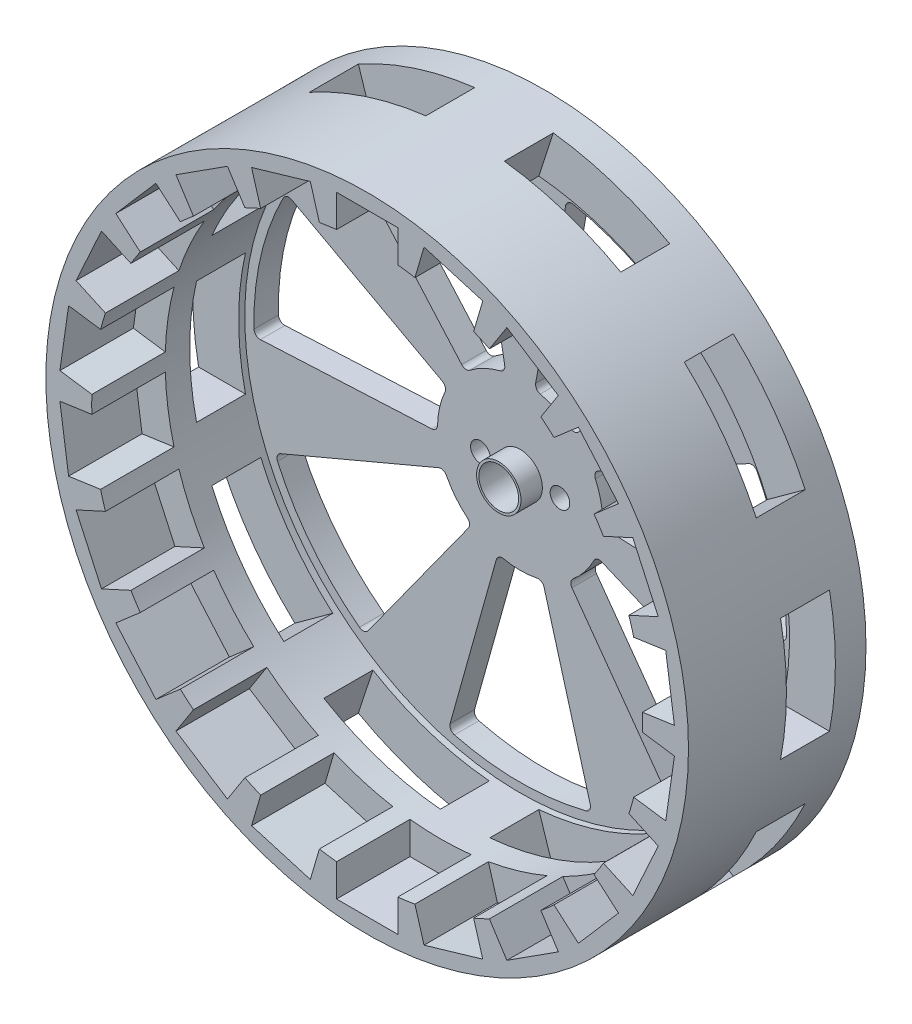
SolidWorks part; units mm, degrees
ref_plane "正面" through (0, 0, 0) normal (0, 0, 1) x (1, 0, 0)
ref_plane "平面" through (0, 0, 0) normal (0, 1, 0) x (1, 0, 0)
ref_plane "右側面" through (0, 0, 0) normal (1, 0, 0) x (0, 0, -1)
sketch "ｽｹｯﾁ1" plane through (0, 0, 0) normal (0, 0, 1) x (1, 0, 0)
  circle A0 centre (0, 0) radius 45
  circle A1 centre (0, 0) radius 52.5
  dimension "D1" = 90
  dimension "D2" = 105
extrude "ﾎﾞｽ - 押し出し1" add sketch "ｽｹｯﾁ1" along normal blind 25
extrude "ﾎﾞｽ - 押し出し2" add sketch "ｽｹｯﾁ1<2>" against normal blind 4 contours A1
sketch "ｽｹｯﾁ1<2>" plane through (0, 0, 0) normal (0, 0, 1) x (1, 0, 0) same geometry as "ｽｹｯﾁ1"
sketch "ｽｹｯﾁ2" plane through (0, 0, -4) normal (0, 0, -1) x (-1, 0, 0)
  line L0 (-6.5, 0) -> (6.5, 0)
  circle A0 centre (0, 0) radius 3.25
  circle A1 centre (6.5, 0) radius 1.6
  circle A2 centre (-6.5, 0) radius 1.6
  point P6 (0, 0)
  dimension "D1" = 6.5
  dimension "D3" = 3.2
  dimension "D4" = 3.2
  dimension "D2" = 6.5
extrude "ｶｯﾄ - 押し出し1" cut sketch "ｽｹｯﾁ2" against normal blind 4 contours A2 | A0 | A1
sketch "ｽｹｯﾁ3" plane through (0, 0, 0) normal (0, 0, 1) x (1, 0, 0)
  circle A0 centre (0, 0) radius 3.25
  circle A1 centre (0, 0) radius 3.625
  dimension "D1" = 6.5
  dimension "D2" = 7.25
extrude "ﾎﾞｽ - 押し出し3" add sketch "ｽｹｯﾁ3" along normal blind 3.5
sketch "ｽｹｯﾁ4" plane through (0, 0, -4) normal (0, 0, -1) x (-1, 0, 0)
  line L6 (-3.6401, -13) -> (-11.7291, -41.8889)
  line L7 (3.6401, -13) -> (11.7291, -41.8889)
  circle A0 centre (0, 0) radius 10
  arc A2 (-3.6401, -13) -> (3.6401, -13) centre (0, 0) ccw
  arc A3 (-11.7291, -41.8889) -> (11.7291, -41.8889) centre (0, 0) ccw
  dimension "D1" = 20
  dimension "D3" = 87
  dimension "D5" = 30
  dimension "D6" = 30
sketch "ｽｹｯﾁ5" plane through (0, 0, 25) normal (0, 0, 1) x (1, 0, 0)
  line L0 (0, 0) -> (0, 45)
  line L1 (0, 45) -> (5, 45)
  line L2 (0, 45) -> (0, 52.5)
  line L3 (0, 45) -> (0, 50)
  line L5 (-5, 40) -> (5, 40)
  line L6 (-5, 40) -> (-5, 50)
  line L7 (-5, 50) -> (5, 50)
  line L8 (5, 40) -> (5, 50)
  line L9 (0, 50) -> (0, 40) construction
  line L10 (-5, 45) -> (5, 45) construction
  circle A0 centre (0, 0) radius 45 construction
  circle A2 centre (0, 0) radius 52.5 construction
  dimension "D1" = 5
  dimension "D2" = 7.5
  dimension "D3" = 5
extrude "ｶｯﾄ - 押し出し4" cut sketch "ｽｹｯﾁ5" against normal blind 12 contours L7 L8 L5 L6
pattern_circular "円形ﾊﾟﾀｰﾝ2" count 22 over 360 about axis through (0, 0, 25) along (0, 0, 1) of "ｶｯﾄ - 押し出し4"
ref_plane "平面1" through (52.5, 0, 0) normal (1, 0, 0) x (0, 0, -1)
sketch "ｽｹｯﾁ7" plane through (52.5, 0, 0) normal (1, 0, 0) x (0, 0, -1)
  line L0 (4, 0) -> (-1, 0)
  line L1 (4, -52.5) -> (4, 52.5) construction
  line L2 (-1, 10) -> (-1, -10)
  line L3 (-1, 10) -> (-9, 10)
  line L4 (-9, 10) -> (-9, -10)
  line L5 (-9, -10) -> (-1, -10)
  point P8 (-1, 0)
  dimension "D1" = 5
  dimension "D2" = 10
  dimension "D3" = 8
extrude "ｶｯﾄ - 押し出し5" cut sketch "ｽｹｯﾁ7" against normal blind 10 contours L4 L5 L2 L3
pattern_circular "円形ﾊﾟﾀｰﾝ3" count 10 over 360 about axis through (0, 0, -4) along (0, 0, 1) of "ｶｯﾄ - 押し出し5"
extrude "ｶｯﾄ - 押し出し6" cut sketch "ｽｹｯﾁ4" against normal blind 10 contours L7 A3 L6 A2
fillet "ﾌｨﾚｯﾄ1" radius 1 4 edges at (-3.6401, -13, -2) (3.6401, -13, -2) (-11.7291, -41.8889, -2) (11.7291, -41.8889, -2)
pattern_circular "円形ﾊﾟﾀｰﾝ4" count 7 over 360 about axis through (0, 0, -4) along (0, 0, 1) of "ｶｯﾄ - 押し出し6", "ﾌｨﾚｯﾄ1"
